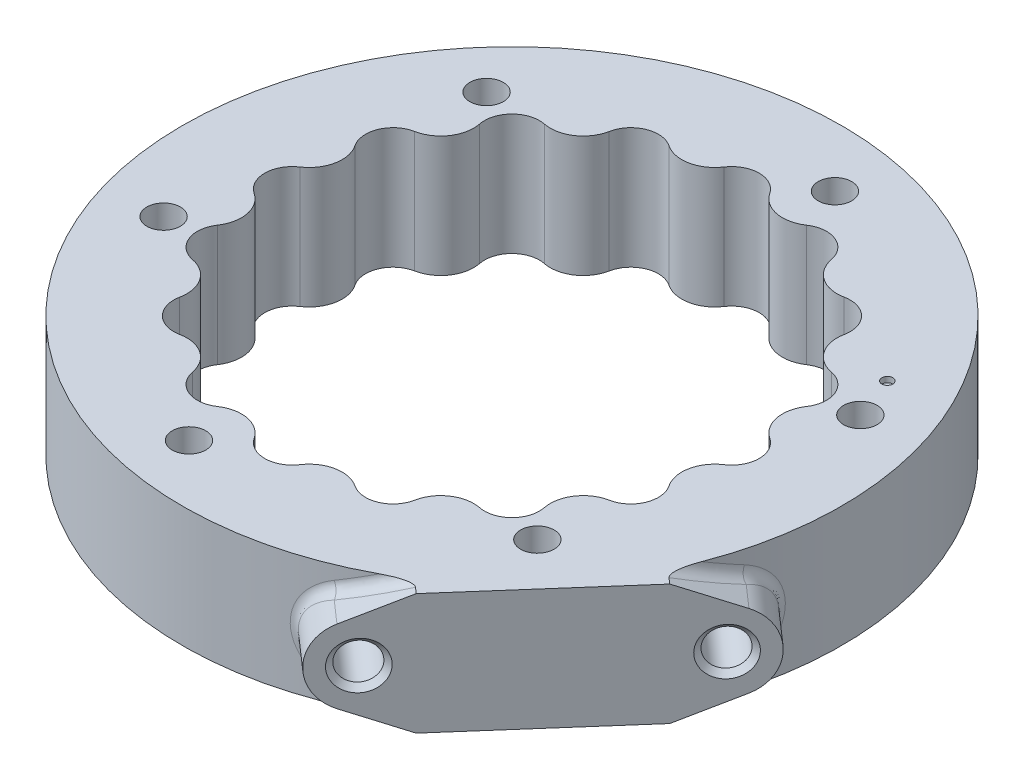
SolidWorks part; units mm, degrees
note: '?' marks a value the reader was unsure of.
ref_plane "Front Plane" through (0, 0, 0) normal (0, 0, 1) x (1, 0, 0)
ref_plane "Top Plane" through (0, 0, 0) normal (0, 1, 0) x (1, 0, 0)
ref_plane "Right Plane" through (0, 0, 0) normal (1, 0, 0) x (0, 0, -1)
sketch "Sketch1" plane through (0, 0, 0) normal (0, 1, 0) x (1, 0, 0)
  arc A0 (-31.5919, 24.5347) -> (-34.7568, 19.7981) centre (0, 0) ccw
  arc A1 (4.9902, 39.6875) -> (-4.9902, 39.6875) centre (0, 40) ccw
  arc A2 (19.7981, 34.7568) -> (10.5774, 38.5761) centre (15.3073, 36.9552) ccw
  arc A3 (-31.5919, 24.5347) -> (-34.7568, 19.7981) centre (0, 0) ccw construction
  arc A4 (31.5919, 24.5347) -> (24.5347, 31.5919) centre (28.2843, 28.2843) ccw
  arc A5 (-31.5919, 24.5347) -> (-34.7568, 19.7981) centre (0, 0) ccw construction
  arc A6 (38.5761, 10.5774) -> (34.7568, 19.7981) centre (36.9552, 15.3073) ccw
  arc A7 (-31.5919, 24.5347) -> (-34.7568, 19.7981) centre (0, 0) ccw construction
  arc A8 (39.6875, -4.9902) -> (39.6875, 4.9902) centre (40, 0) ccw
  arc A9 (-31.5919, 24.5347) -> (-34.7568, 19.7981) centre (0, 0) ccw construction
  arc A10 (34.7568, -19.7981) -> (38.5761, -10.5774) centre (36.9552, -15.3073) ccw
  arc A11 (-31.5919, 24.5347) -> (-34.7568, 19.7981) centre (0, 0) ccw construction
  arc A12 (24.5347, -31.5919) -> (31.5919, -24.5347) centre (28.2843, -28.2843) ccw
  arc A13 (-31.5919, 24.5347) -> (-34.7568, 19.7981) centre (0, 0) ccw construction
  arc A14 (10.5774, -38.5761) -> (19.7981, -34.7568) centre (15.3073, -36.9552) ccw
  arc A15 (-31.5919, 24.5347) -> (-34.7568, 19.7981) centre (0, 0) ccw construction
  arc A16 (-4.9902, -39.6875) -> (4.9902, -39.6875) centre (0, -40) ccw
  arc A17 (-31.5919, 24.5347) -> (-34.7568, 19.7981) centre (0, 0) ccw construction
  arc A18 (-19.7981, -34.7568) -> (-10.5774, -38.5761) centre (-15.3073, -36.9552) ccw
  arc A19 (-31.5919, 24.5347) -> (-34.7568, 19.7981) centre (0, 0) ccw construction
  arc A20 (-31.5919, -24.5347) -> (-24.5347, -31.5919) centre (-28.2843, -28.2843) ccw
  arc A21 (-31.5919, 24.5347) -> (-34.7568, 19.7981) centre (0, 0) ccw construction
  arc A22 (-38.5761, -10.5774) -> (-34.7568, -19.7981) centre (-36.9552, -15.3073) ccw
  arc A23 (-31.5919, 24.5347) -> (-34.7568, 19.7981) centre (0, 0) ccw construction
  arc A24 (-39.6875, 4.9902) -> (-39.6875, -4.9902) centre (-40, 0) ccw
  arc A25 (-31.5919, 24.5347) -> (-34.7568, 19.7981) centre (0, 0) ccw construction
  arc A26 (-34.7568, 19.7981) -> (-38.5761, 10.5774) centre (-36.9552, 15.3073) ccw
  arc A27 (-31.5919, 24.5347) -> (-34.7568, 19.7981) centre (0, 0) ccw construction
  arc A28 (-24.5347, 31.5919) -> (-31.5919, 24.5347) centre (-28.2843, 28.2843) ccw
  arc A29 (-31.5919, 24.5347) -> (-34.7568, 19.7981) centre (0, 0) ccw construction
  arc A30 (-10.5774, 38.5761) -> (-19.7981, 34.7568) centre (-15.3073, 36.9552) ccw
  arc A31 (-31.5919, 24.5347) -> (-34.7568, 19.7981) centre (0, 0) ccw construction
  circle A32 centre (0, 0) radius 60
  arc A33 (-19.7981, 34.7568) -> (-24.5347, 31.5919) centre (0, 0) ccw
  arc A34 (-19.7981, 34.7568) -> (-24.5347, 31.5919) centre (0, 0) ccw construction
  arc A35 (-19.7981, 34.7568) -> (-24.5347, 31.5919) centre (0, 0) ccw construction
  arc A36 (-19.7981, 34.7568) -> (-24.5347, 31.5919) centre (0, 0) ccw construction
  arc A37 (-19.7981, 34.7568) -> (-24.5347, 31.5919) centre (0, 0) ccw construction
  arc A38 (-19.7981, 34.7568) -> (-24.5347, 31.5919) centre (0, 0) ccw construction
  arc A39 (-19.7981, 34.7568) -> (-24.5347, 31.5919) centre (0, 0) ccw construction
  arc A40 (-19.7981, 34.7568) -> (-24.5347, 31.5919) centre (0, 0) ccw construction
  arc A41 (-19.7981, 34.7568) -> (-24.5347, 31.5919) centre (0, 0) ccw construction
  arc A42 (-19.7981, 34.7568) -> (-24.5347, 31.5919) centre (0, 0) ccw construction
  arc A43 (-19.7981, 34.7568) -> (-24.5347, 31.5919) centre (0, 0) ccw construction
  arc A44 (-19.7981, 34.7568) -> (-24.5347, 31.5919) centre (0, 0) ccw construction
  arc A45 (-19.7981, 34.7568) -> (-24.5347, 31.5919) centre (0, 0) ccw construction
  arc A46 (-19.7981, 34.7568) -> (-24.5347, 31.5919) centre (0, 0) ccw construction
  arc A47 (-19.7981, 34.7568) -> (-24.5347, 31.5919) centre (0, 0) ccw construction
  arc A48 (-19.7981, 34.7568) -> (-24.5347, 31.5919) centre (0, 0) ccw construction
  arc A49 (-4.9902, 39.6875) -> (-10.5774, 38.5761) centre (0, 0) ccw
  arc A50 (-4.9902, 39.6875) -> (-10.5774, 38.5761) centre (0, 0) ccw construction
  arc A51 (-4.9902, 39.6875) -> (-10.5774, 38.5761) centre (0, 0) ccw construction
  arc A52 (-4.9902, 39.6875) -> (-10.5774, 38.5761) centre (0, 0) ccw construction
  arc A53 (-4.9902, 39.6875) -> (-10.5774, 38.5761) centre (0, 0) ccw construction
  arc A54 (-4.9902, 39.6875) -> (-10.5774, 38.5761) centre (0, 0) ccw construction
  arc A55 (-4.9902, 39.6875) -> (-10.5774, 38.5761) centre (0, 0) ccw construction
  arc A56 (-4.9902, 39.6875) -> (-10.5774, 38.5761) centre (0, 0) ccw construction
  arc A57 (-4.9902, 39.6875) -> (-10.5774, 38.5761) centre (0, 0) ccw construction
  arc A58 (-4.9902, 39.6875) -> (-10.5774, 38.5761) centre (0, 0) ccw construction
  arc A59 (-4.9902, 39.6875) -> (-10.5774, 38.5761) centre (0, 0) ccw construction
  arc A60 (-4.9902, 39.6875) -> (-10.5774, 38.5761) centre (0, 0) ccw construction
  arc A61 (-4.9902, 39.6875) -> (-10.5774, 38.5761) centre (0, 0) ccw construction
  arc A62 (-4.9902, 39.6875) -> (-10.5774, 38.5761) centre (0, 0) ccw construction
  arc A63 (-4.9902, 39.6875) -> (-10.5774, 38.5761) centre (0, 0) ccw construction
  arc A64 (-4.9902, 39.6875) -> (-10.5774, 38.5761) centre (0, 0) ccw construction
  arc A65 (10.5774, 38.5761) -> (4.9902, 39.6875) centre (0, 0) ccw
  arc A66 (10.5774, 38.5761) -> (4.9902, 39.6875) centre (0, 0) ccw construction
  arc A67 (10.5774, 38.5761) -> (4.9902, 39.6875) centre (0, 0) ccw construction
  arc A68 (10.5774, 38.5761) -> (4.9902, 39.6875) centre (0, 0) ccw construction
  arc A69 (10.5774, 38.5761) -> (4.9902, 39.6875) centre (0, 0) ccw construction
  arc A70 (10.5774, 38.5761) -> (4.9902, 39.6875) centre (0, 0) ccw construction
  arc A71 (10.5774, 38.5761) -> (4.9902, 39.6875) centre (0, 0) ccw construction
  arc A72 (10.5774, 38.5761) -> (4.9902, 39.6875) centre (0, 0) ccw construction
  arc A73 (10.5774, 38.5761) -> (4.9902, 39.6875) centre (0, 0) ccw construction
  arc A74 (10.5774, 38.5761) -> (4.9902, 39.6875) centre (0, 0) ccw construction
  arc A75 (10.5774, 38.5761) -> (4.9902, 39.6875) centre (0, 0) ccw construction
  arc A76 (10.5774, 38.5761) -> (4.9902, 39.6875) centre (0, 0) ccw construction
  arc A77 (10.5774, 38.5761) -> (4.9902, 39.6875) centre (0, 0) ccw construction
  arc A78 (10.5774, 38.5761) -> (4.9902, 39.6875) centre (0, 0) ccw construction
  arc A79 (10.5774, 38.5761) -> (4.9902, 39.6875) centre (0, 0) ccw construction
  arc A80 (10.5774, 38.5761) -> (4.9902, 39.6875) centre (0, 0) ccw construction
  arc A81 (24.5347, 31.5919) -> (19.7981, 34.7568) centre (0, 0) ccw
  arc A82 (24.5347, 31.5919) -> (19.7981, 34.7568) centre (0, 0) ccw construction
  arc A83 (24.5347, 31.5919) -> (19.7981, 34.7568) centre (0, 0) ccw construction
  arc A84 (24.5347, 31.5919) -> (19.7981, 34.7568) centre (0, 0) ccw construction
  arc A85 (24.5347, 31.5919) -> (19.7981, 34.7568) centre (0, 0) ccw construction
  arc A86 (24.5347, 31.5919) -> (19.7981, 34.7568) centre (0, 0) ccw construction
  arc A87 (24.5347, 31.5919) -> (19.7981, 34.7568) centre (0, 0) ccw construction
  arc A88 (24.5347, 31.5919) -> (19.7981, 34.7568) centre (0, 0) ccw construction
  arc A89 (24.5347, 31.5919) -> (19.7981, 34.7568) centre (0, 0) ccw construction
  arc A90 (24.5347, 31.5919) -> (19.7981, 34.7568) centre (0, 0) ccw construction
  arc A91 (24.5347, 31.5919) -> (19.7981, 34.7568) centre (0, 0) ccw construction
  arc A92 (24.5347, 31.5919) -> (19.7981, 34.7568) centre (0, 0) ccw construction
  arc A93 (24.5347, 31.5919) -> (19.7981, 34.7568) centre (0, 0) ccw construction
  arc A94 (24.5347, 31.5919) -> (19.7981, 34.7568) centre (0, 0) ccw construction
  arc A95 (24.5347, 31.5919) -> (19.7981, 34.7568) centre (0, 0) ccw construction
  arc A96 (24.5347, 31.5919) -> (19.7981, 34.7568) centre (0, 0) ccw construction
  arc A97 (34.7568, 19.7981) -> (31.5919, 24.5347) centre (0, 0) ccw
  arc A98 (34.7568, 19.7981) -> (31.5919, 24.5347) centre (0, 0) ccw construction
  arc A99 (34.7568, 19.7981) -> (31.5919, 24.5347) centre (0, 0) ccw construction
  arc A100 (34.7568, 19.7981) -> (31.5919, 24.5347) centre (0, 0) ccw construction
  arc A101 (34.7568, 19.7981) -> (31.5919, 24.5347) centre (0, 0) ccw construction
  arc A102 (34.7568, 19.7981) -> (31.5919, 24.5347) centre (0, 0) ccw construction
  arc A103 (34.7568, 19.7981) -> (31.5919, 24.5347) centre (0, 0) ccw construction
  arc A104 (34.7568, 19.7981) -> (31.5919, 24.5347) centre (0, 0) ccw construction
  arc A105 (34.7568, 19.7981) -> (31.5919, 24.5347) centre (0, 0) ccw construction
  arc A106 (34.7568, 19.7981) -> (31.5919, 24.5347) centre (0, 0) ccw construction
  arc A107 (34.7568, 19.7981) -> (31.5919, 24.5347) centre (0, 0) ccw construction
  arc A108 (34.7568, 19.7981) -> (31.5919, 24.5347) centre (0, 0) ccw construction
  arc A109 (34.7568, 19.7981) -> (31.5919, 24.5347) centre (0, 0) ccw construction
  arc A110 (34.7568, 19.7981) -> (31.5919, 24.5347) centre (0, 0) ccw construction
  arc A111 (34.7568, 19.7981) -> (31.5919, 24.5347) centre (0, 0) ccw construction
  arc A112 (34.7568, 19.7981) -> (31.5919, 24.5347) centre (0, 0) ccw construction
  arc A113 (39.6875, 4.9902) -> (38.5761, 10.5774) centre (0, 0) ccw
  arc A114 (39.6875, 4.9902) -> (38.5761, 10.5774) centre (0, 0) ccw construction
  arc A115 (39.6875, 4.9902) -> (38.5761, 10.5774) centre (0, 0) ccw construction
  arc A116 (39.6875, 4.9902) -> (38.5761, 10.5774) centre (0, 0) ccw construction
  arc A117 (39.6875, 4.9902) -> (38.5761, 10.5774) centre (0, 0) ccw construction
  arc A118 (39.6875, 4.9902) -> (38.5761, 10.5774) centre (0, 0) ccw construction
  arc A119 (39.6875, 4.9902) -> (38.5761, 10.5774) centre (0, 0) ccw construction
  arc A120 (39.6875, 4.9902) -> (38.5761, 10.5774) centre (0, 0) ccw construction
  arc A121 (39.6875, 4.9902) -> (38.5761, 10.5774) centre (0, 0) ccw construction
  arc A122 (39.6875, 4.9902) -> (38.5761, 10.5774) centre (0, 0) ccw construction
  arc A123 (39.6875, 4.9902) -> (38.5761, 10.5774) centre (0, 0) ccw construction
  arc A124 (39.6875, 4.9902) -> (38.5761, 10.5774) centre (0, 0) ccw construction
  arc A125 (39.6875, 4.9902) -> (38.5761, 10.5774) centre (0, 0) ccw construction
  arc A126 (39.6875, 4.9902) -> (38.5761, 10.5774) centre (0, 0) ccw construction
  arc A127 (39.6875, 4.9902) -> (38.5761, 10.5774) centre (0, 0) ccw construction
  arc A128 (39.6875, 4.9902) -> (38.5761, 10.5774) centre (0, 0) ccw construction
  arc A129 (38.5761, -10.5774) -> (39.6875, -4.9902) centre (0, 0) ccw
  arc A130 (38.5761, -10.5774) -> (39.6875, -4.9902) centre (0, 0) ccw construction
  arc A131 (38.5761, -10.5774) -> (39.6875, -4.9902) centre (0, 0) ccw construction
  arc A132 (38.5761, -10.5774) -> (39.6875, -4.9902) centre (0, 0) ccw construction
  arc A133 (38.5761, -10.5774) -> (39.6875, -4.9902) centre (0, 0) ccw construction
  arc A134 (38.5761, -10.5774) -> (39.6875, -4.9902) centre (0, 0) ccw construction
  arc A135 (38.5761, -10.5774) -> (39.6875, -4.9902) centre (0, 0) ccw construction
  arc A136 (38.5761, -10.5774) -> (39.6875, -4.9902) centre (0, 0) ccw construction
  arc A137 (38.5761, -10.5774) -> (39.6875, -4.9902) centre (0, 0) ccw construction
  arc A138 (38.5761, -10.5774) -> (39.6875, -4.9902) centre (0, 0) ccw construction
  arc A139 (38.5761, -10.5774) -> (39.6875, -4.9902) centre (0, 0) ccw construction
  arc A140 (38.5761, -10.5774) -> (39.6875, -4.9902) centre (0, 0) ccw construction
  arc A141 (38.5761, -10.5774) -> (39.6875, -4.9902) centre (0, 0) ccw construction
  arc A142 (38.5761, -10.5774) -> (39.6875, -4.9902) centre (0, 0) ccw construction
  arc A143 (38.5761, -10.5774) -> (39.6875, -4.9902) centre (0, 0) ccw construction
  arc A144 (38.5761, -10.5774) -> (39.6875, -4.9902) centre (0, 0) ccw construction
  arc A145 (31.5919, -24.5347) -> (34.7568, -19.7981) centre (0, 0) ccw
  arc A146 (31.5919, -24.5347) -> (34.7568, -19.7981) centre (0, 0) ccw construction
  arc A147 (31.5919, -24.5347) -> (34.7568, -19.7981) centre (0, 0) ccw construction
  arc A148 (31.5919, -24.5347) -> (34.7568, -19.7981) centre (0, 0) ccw construction
  arc A149 (31.5919, -24.5347) -> (34.7568, -19.7981) centre (0, 0) ccw construction
  arc A150 (31.5919, -24.5347) -> (34.7568, -19.7981) centre (0, 0) ccw construction
  arc A151 (31.5919, -24.5347) -> (34.7568, -19.7981) centre (0, 0) ccw construction
  arc A152 (31.5919, -24.5347) -> (34.7568, -19.7981) centre (0, 0) ccw construction
  arc A153 (31.5919, -24.5347) -> (34.7568, -19.7981) centre (0, 0) ccw construction
  arc A154 (31.5919, -24.5347) -> (34.7568, -19.7981) centre (0, 0) ccw construction
  arc A155 (31.5919, -24.5347) -> (34.7568, -19.7981) centre (0, 0) ccw construction
  arc A156 (31.5919, -24.5347) -> (34.7568, -19.7981) centre (0, 0) ccw construction
  arc A157 (31.5919, -24.5347) -> (34.7568, -19.7981) centre (0, 0) ccw construction
  arc A158 (31.5919, -24.5347) -> (34.7568, -19.7981) centre (0, 0) ccw construction
  arc A159 (31.5919, -24.5347) -> (34.7568, -19.7981) centre (0, 0) ccw construction
  arc A160 (31.5919, -24.5347) -> (34.7568, -19.7981) centre (0, 0) ccw construction
  arc A161 (19.7981, -34.7568) -> (24.5347, -31.5919) centre (0, 0) ccw
  arc A162 (19.7981, -34.7568) -> (24.5347, -31.5919) centre (0, 0) ccw construction
  arc A163 (19.7981, -34.7568) -> (24.5347, -31.5919) centre (0, 0) ccw construction
  arc A164 (19.7981, -34.7568) -> (24.5347, -31.5919) centre (0, 0) ccw construction
  arc A165 (19.7981, -34.7568) -> (24.5347, -31.5919) centre (0, 0) ccw construction
  arc A166 (19.7981, -34.7568) -> (24.5347, -31.5919) centre (0, 0) ccw construction
  arc A167 (19.7981, -34.7568) -> (24.5347, -31.5919) centre (0, 0) ccw construction
  arc A168 (19.7981, -34.7568) -> (24.5347, -31.5919) centre (0, 0) ccw construction
  arc A169 (19.7981, -34.7568) -> (24.5347, -31.5919) centre (0, 0) ccw construction
  arc A170 (19.7981, -34.7568) -> (24.5347, -31.5919) centre (0, 0) ccw construction
  arc A171 (19.7981, -34.7568) -> (24.5347, -31.5919) centre (0, 0) ccw construction
  arc A172 (19.7981, -34.7568) -> (24.5347, -31.5919) centre (0, 0) ccw construction
  arc A173 (19.7981, -34.7568) -> (24.5347, -31.5919) centre (0, 0) ccw construction
  arc A174 (19.7981, -34.7568) -> (24.5347, -31.5919) centre (0, 0) ccw construction
  arc A175 (19.7981, -34.7568) -> (24.5347, -31.5919) centre (0, 0) ccw construction
  arc A176 (19.7981, -34.7568) -> (24.5347, -31.5919) centre (0, 0) ccw construction
  arc A177 (4.9902, -39.6875) -> (10.5774, -38.5761) centre (0, 0) ccw
  arc A178 (4.9902, -39.6875) -> (10.5774, -38.5761) centre (0, 0) ccw construction
  arc A179 (4.9902, -39.6875) -> (10.5774, -38.5761) centre (0, 0) ccw construction
  arc A180 (4.9902, -39.6875) -> (10.5774, -38.5761) centre (0, 0) ccw construction
  arc A181 (4.9902, -39.6875) -> (10.5774, -38.5761) centre (0, 0) ccw construction
  arc A182 (4.9902, -39.6875) -> (10.5774, -38.5761) centre (0, 0) ccw construction
  arc A183 (4.9902, -39.6875) -> (10.5774, -38.5761) centre (0, 0) ccw construction
  arc A184 (4.9902, -39.6875) -> (10.5774, -38.5761) centre (0, 0) ccw construction
  arc A185 (4.9902, -39.6875) -> (10.5774, -38.5761) centre (0, 0) ccw construction
  arc A186 (4.9902, -39.6875) -> (10.5774, -38.5761) centre (0, 0) ccw construction
  arc A187 (4.9902, -39.6875) -> (10.5774, -38.5761) centre (0, 0) ccw construction
  arc A188 (4.9902, -39.6875) -> (10.5774, -38.5761) centre (0, 0) ccw construction
  arc A189 (4.9902, -39.6875) -> (10.5774, -38.5761) centre (0, 0) ccw construction
  arc A190 (4.9902, -39.6875) -> (10.5774, -38.5761) centre (0, 0) ccw construction
  arc A191 (4.9902, -39.6875) -> (10.5774, -38.5761) centre (0, 0) ccw construction
  arc A192 (4.9902, -39.6875) -> (10.5774, -38.5761) centre (0, 0) ccw construction
  arc A193 (-10.5774, -38.5761) -> (-4.9902, -39.6875) centre (0, 0) ccw
  arc A194 (-10.5774, -38.5761) -> (-4.9902, -39.6875) centre (0, 0) ccw construction
  arc A195 (-10.5774, -38.5761) -> (-4.9902, -39.6875) centre (0, 0) ccw construction
  arc A196 (-10.5774, -38.5761) -> (-4.9902, -39.6875) centre (0, 0) ccw construction
  arc A197 (-10.5774, -38.5761) -> (-4.9902, -39.6875) centre (0, 0) ccw construction
  arc A198 (-10.5774, -38.5761) -> (-4.9902, -39.6875) centre (0, 0) ccw construction
  arc A199 (-10.5774, -38.5761) -> (-4.9902, -39.6875) centre (0, 0) ccw construction
  arc A200 (-10.5774, -38.5761) -> (-4.9902, -39.6875) centre (0, 0) ccw construction
  arc A201 (-10.5774, -38.5761) -> (-4.9902, -39.6875) centre (0, 0) ccw construction
  arc A202 (-10.5774, -38.5761) -> (-4.9902, -39.6875) centre (0, 0) ccw construction
  arc A203 (-10.5774, -38.5761) -> (-4.9902, -39.6875) centre (0, 0) ccw construction
  arc A204 (-10.5774, -38.5761) -> (-4.9902, -39.6875) centre (0, 0) ccw construction
  arc A205 (-10.5774, -38.5761) -> (-4.9902, -39.6875) centre (0, 0) ccw construction
  arc A206 (-10.5774, -38.5761) -> (-4.9902, -39.6875) centre (0, 0) ccw construction
  arc A207 (-10.5774, -38.5761) -> (-4.9902, -39.6875) centre (0, 0) ccw construction
  arc A208 (-10.5774, -38.5761) -> (-4.9902, -39.6875) centre (0, 0) ccw construction
  arc A209 (-24.5347, -31.5919) -> (-19.7981, -34.7568) centre (0, 0) ccw
  arc A210 (-24.5347, -31.5919) -> (-19.7981, -34.7568) centre (0, 0) ccw construction
  arc A211 (-24.5347, -31.5919) -> (-19.7981, -34.7568) centre (0, 0) ccw construction
  arc A212 (-24.5347, -31.5919) -> (-19.7981, -34.7568) centre (0, 0) ccw construction
  arc A213 (-24.5347, -31.5919) -> (-19.7981, -34.7568) centre (0, 0) ccw construction
  arc A214 (-24.5347, -31.5919) -> (-19.7981, -34.7568) centre (0, 0) ccw construction
  arc A215 (-24.5347, -31.5919) -> (-19.7981, -34.7568) centre (0, 0) ccw construction
  arc A216 (-24.5347, -31.5919) -> (-19.7981, -34.7568) centre (0, 0) ccw construction
  arc A217 (-24.5347, -31.5919) -> (-19.7981, -34.7568) centre (0, 0) ccw construction
  arc A218 (-24.5347, -31.5919) -> (-19.7981, -34.7568) centre (0, 0) ccw construction
  arc A219 (-24.5347, -31.5919) -> (-19.7981, -34.7568) centre (0, 0) ccw construction
  arc A220 (-24.5347, -31.5919) -> (-19.7981, -34.7568) centre (0, 0) ccw construction
  arc A221 (-24.5347, -31.5919) -> (-19.7981, -34.7568) centre (0, 0) ccw construction
  arc A222 (-24.5347, -31.5919) -> (-19.7981, -34.7568) centre (0, 0) ccw construction
  arc A223 (-24.5347, -31.5919) -> (-19.7981, -34.7568) centre (0, 0) ccw construction
  arc A224 (-24.5347, -31.5919) -> (-19.7981, -34.7568) centre (0, 0) ccw construction
  arc A225 (-34.7568, -19.7981) -> (-31.5919, -24.5347) centre (0, 0) ccw
  arc A226 (-34.7568, -19.7981) -> (-31.5919, -24.5347) centre (0, 0) ccw construction
  arc A227 (-34.7568, -19.7981) -> (-31.5919, -24.5347) centre (0, 0) ccw construction
  arc A228 (-34.7568, -19.7981) -> (-31.5919, -24.5347) centre (0, 0) ccw construction
  arc A229 (-34.7568, -19.7981) -> (-31.5919, -24.5347) centre (0, 0) ccw construction
  arc A230 (-34.7568, -19.7981) -> (-31.5919, -24.5347) centre (0, 0) ccw construction
  arc A231 (-34.7568, -19.7981) -> (-31.5919, -24.5347) centre (0, 0) ccw construction
  arc A232 (-34.7568, -19.7981) -> (-31.5919, -24.5347) centre (0, 0) ccw construction
  arc A233 (-34.7568, -19.7981) -> (-31.5919, -24.5347) centre (0, 0) ccw construction
  arc A234 (-34.7568, -19.7981) -> (-31.5919, -24.5347) centre (0, 0) ccw construction
  arc A235 (-34.7568, -19.7981) -> (-31.5919, -24.5347) centre (0, 0) ccw construction
  arc A236 (-34.7568, -19.7981) -> (-31.5919, -24.5347) centre (0, 0) ccw construction
  arc A237 (-34.7568, -19.7981) -> (-31.5919, -24.5347) centre (0, 0) ccw construction
  arc A238 (-34.7568, -19.7981) -> (-31.5919, -24.5347) centre (0, 0) ccw construction
  arc A239 (-34.7568, -19.7981) -> (-31.5919, -24.5347) centre (0, 0) ccw construction
  arc A240 (-34.7568, -19.7981) -> (-31.5919, -24.5347) centre (0, 0) ccw construction
  arc A241 (-39.6875, -4.9902) -> (-38.5761, -10.5774) centre (0, 0) ccw
  arc A242 (-39.6875, -4.9902) -> (-38.5761, -10.5774) centre (0, 0) ccw construction
  arc A243 (-39.6875, -4.9902) -> (-38.5761, -10.5774) centre (0, 0) ccw construction
  arc A244 (-39.6875, -4.9902) -> (-38.5761, -10.5774) centre (0, 0) ccw construction
  arc A245 (-39.6875, -4.9902) -> (-38.5761, -10.5774) centre (0, 0) ccw construction
  arc A246 (-39.6875, -4.9902) -> (-38.5761, -10.5774) centre (0, 0) ccw construction
  arc A247 (-39.6875, -4.9902) -> (-38.5761, -10.5774) centre (0, 0) ccw construction
  arc A248 (-39.6875, -4.9902) -> (-38.5761, -10.5774) centre (0, 0) ccw construction
  arc A249 (-39.6875, -4.9902) -> (-38.5761, -10.5774) centre (0, 0) ccw construction
  arc A250 (-39.6875, -4.9902) -> (-38.5761, -10.5774) centre (0, 0) ccw construction
  arc A251 (-39.6875, -4.9902) -> (-38.5761, -10.5774) centre (0, 0) ccw construction
  arc A252 (-39.6875, -4.9902) -> (-38.5761, -10.5774) centre (0, 0) ccw construction
  arc A253 (-39.6875, -4.9902) -> (-38.5761, -10.5774) centre (0, 0) ccw construction
  arc A254 (-39.6875, -4.9902) -> (-38.5761, -10.5774) centre (0, 0) ccw construction
  arc A255 (-39.6875, -4.9902) -> (-38.5761, -10.5774) centre (0, 0) ccw construction
  arc A256 (-39.6875, -4.9902) -> (-38.5761, -10.5774) centre (0, 0) ccw construction
  arc A257 (-38.5761, 10.5774) -> (-39.6875, 4.9902) centre (0, 0) ccw
  arc A258 (-38.5761, 10.5774) -> (-39.6875, 4.9902) centre (0, 0) ccw construction
  arc A259 (-38.5761, 10.5774) -> (-39.6875, 4.9902) centre (0, 0) ccw construction
  arc A260 (-38.5761, 10.5774) -> (-39.6875, 4.9902) centre (0, 0) ccw construction
  arc A261 (-38.5761, 10.5774) -> (-39.6875, 4.9902) centre (0, 0) ccw construction
  arc A262 (-38.5761, 10.5774) -> (-39.6875, 4.9902) centre (0, 0) ccw construction
  arc A263 (-38.5761, 10.5774) -> (-39.6875, 4.9902) centre (0, 0) ccw construction
  arc A264 (-38.5761, 10.5774) -> (-39.6875, 4.9902) centre (0, 0) ccw construction
  arc A265 (-38.5761, 10.5774) -> (-39.6875, 4.9902) centre (0, 0) ccw construction
  arc A266 (-38.5761, 10.5774) -> (-39.6875, 4.9902) centre (0, 0) ccw construction
  arc A267 (-38.5761, 10.5774) -> (-39.6875, 4.9902) centre (0, 0) ccw construction
  arc A268 (-38.5761, 10.5774) -> (-39.6875, 4.9902) centre (0, 0) ccw construction
  arc A269 (-38.5761, 10.5774) -> (-39.6875, 4.9902) centre (0, 0) ccw construction
  arc A270 (-38.5761, 10.5774) -> (-39.6875, 4.9902) centre (0, 0) ccw construction
  arc A271 (-38.5761, 10.5774) -> (-39.6875, 4.9902) centre (0, 0) ccw construction
  arc A272 (-38.5761, 10.5774) -> (-39.6875, 4.9902) centre (0, 0) ccw construction
  point P52 (0, 0)
  dimension "D1" = 80
  dimension "D2" = 10
  dimension "D4" = 120
  dimension "D3" = 16
extrude "Boss-Extrude1" add sketch "Sketch1" along normal blind 22
fillet "Fillet1" radius 5 32 edges at (-31.5919, 11, -24.5347) (-34.7568, 11, -19.7981) (10.5774, 11, 38.5761) (4.9902, 11, 39.6875) (-4.9902, 11, 39.6875) (-10.5774, 11, 38.5761) (-19.7981, 11, 34.7568) (-24.5347, 11, 31.5919) (-31.5919, 11, 24.5347) (-34.7568, 11, 19.7981) (-38.5761, 11, 10.5774) (-39.6875, 11, 4.9902) (-39.6875, 11, -4.9902) (-38.5761, 11, -10.5774) (19.7981, 11, 34.7568) (24.5347, 11, 31.5919) (31.5919, 11, 24.5347) (34.7568, 11, 19.7981) (38.5761, 11, 10.5774) (39.6875, 11, 4.9902) (39.6875, 11, -4.9902) (38.5761, 11, -10.5774) (34.7568, 11, -19.7981) (31.5919, 11, -24.5347) (24.5347, 11, -31.5919) (19.7981, 11, -34.7568) (10.5774, 11, -38.5761) (4.9902, 11, -39.6875) (-4.9902, 11, -39.6875) (-10.5774, 11, -38.5761) (-19.7981, 11, -34.7568) (-24.5347, 11, -31.5919)
fillet "Fillet2" radius 6 16 edges at (-7.8059, 11, 39.2431) (7.8059, 11, 39.2431) (22.2294, 11, 33.2687) (33.2687, 11, 22.2294) (-22.2294, 11, 33.2687) (-33.2687, 11, 22.2294) (-39.2431, 11, 7.8059) (-39.2431, 11, -7.8059) (39.2431, 11, 7.8059) (39.2431, 11, -7.8059) (33.2687, 11, -22.2294) (22.2294, 11, -33.2687) (7.8059, 11, -39.2431) (-7.8059, 11, -39.2431) (-22.2294, 11, -33.2687) (-33.2687, 11, -22.2294)
sketch "Sketch3" plane through (0, 22, 0) normal (0, 1, 0) x (1, 0, 0)
  line L0 (7.9956, 40.1966) -> (11.7054, 58.8471) construction
  circle A0 centre (0, 0) radius 50 construction
  circle A4 centre (9.7545, 49.0393) radius 3.05
  arc A5 (4.1664, 42.7642) -> (12.5159, 41.1034) centre (9.1661, 46.0813) ccw construction
  circle A6 centre (0, 0) radius 60 construction
  circle A7 centre (47.3465, 16.072) radius 3.05
  circle A8 centre (37.592, -32.9673) radius 3.05
  circle A9 centre (-9.7545, -49.0393) radius 3.05
  circle A10 centre (-47.3465, -16.072) radius 3.05
  circle A11 centre (-37.592, 32.9673) radius 3.05
  point P13 (9.1661, 46.0813)
  point P31 (0, 0)
  dimension "D1" = 100
  dimension "D2" = 6.1
  dimension "D3" = 6
extrude "Cut-Extrude1" cut sketch "Sketch3" against normal through all
ref_axis "Axis1" through (37.592, 0, 32.9673) along (0, 1, 0)?
ref_axis "Axis2" through (-9.7545, 0, 49.0393) along (0, 1, 0)?
ref_plane "Plane1" through (13.9187, 0, 41.0033) normal (-0.3214, 0, -0.9469) x (-0.9469, 0, 0.3214)
ref_plane "Plane2" through (19.2864, 0, 56.8158) normal (0.3214, 0, 0.9469) x (0.9469, 0, -0.3214)
ref_plane "Plane3" through (19.6078, 0, 57.7627) normal (0.3214, 0, 0.9469) x (0.9469, 0, -0.3214)
ref_plane "Plane4" through (45.1104, 0, 39.5607) normal (0.7518, 0, 0.6593) x (0, -1, 0)
ref_plane "Plane5" through (45.8622, 0, 40.2201) normal (0.7518, 0, 0.6593) x (0, -1, 0)
sketch "Sketch6" plane through (48.3229, 0, 37.4142) normal (-0.7518, 0, -0.6593) x (-0.6593, 0, 0.7518)
  line L0 (-56.2679, 0) -> (63.7321, 0) construction
  line L1 (-22.8416, 17.6775) -> (-2.6943, 26.1971)
  line L2 (10.1584, 26.1971) -> (30.3057, 17.6775)
  line L3 (-22.8416, 4.3225) -> (-2.6943, -4.1971)
  line L4 (10.1584, -4.1971) -> (30.3057, 4.3225)
  arc A0 (-2.6943, -4.1971) -> (10.1584, -4.1971) centre (3.7321, 11) ccw
  arc A1 (30.3057, 4.3225) -> (30.3057, 17.6775) centre (27.4821, 11) ccw
  arc A2 (-22.8416, 17.6775) -> (-22.8416, 4.3225) centre (-20.0179, 11) ccw
  arc A3 (10.1584, 26.1971) -> (-2.6943, 26.1971) centre (3.7321, 11) ccw
  dimension "D1" = 33
  dimension "D2" = 23.75
  dimension "D3" = 23.75
  dimension "D4" = 11
extrude "Boss-Extrude3" add sketch "Sketch6" against normal up to surface (1.3451 mm away)
sketch "Sketch7" plane through (45.8622, 0, 40.2201) normal (0.7518, 0, 0.6593) x (0.6593, 0, -0.7518)
  circle A0 centre (23.75, 11) radius 3.3
  circle A1 centre (-23.75, 11) radius 3.3
  dimension "D1" = 6.6
extrude "Cut-Extrude3" cut sketch "Sketch7" against normal blind 10.5
chamfer "Chamfer2" distance 1 angle 45 2 edges at (63.6975, 11, 19.8828) (32.3786, 11, 55.5952)
fillet "Fillet3" radius 2 6 edges at (56.3102, 19.8007, 20.7161) (56.3102, 2.1993, 20.7161) (27.8889, 2.1993, 53.1245) (27.8889, 19.8007, 53.1245) (59.03, 9.4978, 10.745) (18.3581, 12.5022, 57.1225)
sketch "Sketch8" plane through (45.8622, 0, 40.2201) normal (0.7518, 0, 0.6593) x (0.6593, 0, -0.7518)
  line L1 (-16.3518, 22) -> (16.3518, 22)
  line L2 (-16.3518, 22) -> (-16.3518, 27.5)
  line L3 (-16.3518, 27.5) -> (16.3518, 27.5)
  line L4 (16.3518, 22) -> (16.3518, 27.5)
  line L6 (-16.3518, -5.5) -> (16.3518, -5.5)
  line L7 (-16.3518, -5.5) -> (-16.3518, 0)
  line L8 (-16.3518, 0) -> (16.3518, 0)
  line L9 (16.3518, -5.5) -> (16.3518, 0)
  line L10 (26.5737, 4.3225) -> (6.4263, -4.1971) construction
  line L11 (60, 22) -> (-60, 22) construction
  arc A0 (6.4263, 26.1971) -> (-6.4263, 26.1971) centre (0, 11) ccw construction
  arc A1 (-6.4263, -4.1971) -> (6.4263, -4.1971) centre (0, 11) ccw construction
extrude "Cut-Extrude4" cut sketch "Sketch8" against normal through all
sketch "Sketch9" [suppressed] plane through (0, 22, 0) normal (0, 1, 0) x (1, 0, 0)
  circle A0 centre (44.4252, 23.9053) radius 1
  dimension "D1" = 2
extrude "Cut-Extrude5" [suppressed] cut sketch "Sketch9" against normal blind 1
sketch "Sketch10" plane through (0, 22, 0) normal (0, 1, 0) x (1, 0, 0)
  circle A0 centre (44.4252, 23.9053) radius 1
  dimension "D1" = 2
extrude "Cut-Extrude6" cut sketch "Sketch10" against normal blind 1
equation "\"R_ROLL\"= 5mm"
equation "\"D_SUN\"= 80mm"
equation "\"NUM_ROLL\"= 16"
equation "\"RHO\"= 1mm"
equation "\"D_SHAFT\"= 15mm"
equation "\"D_OUTPUT\"= 40mm"
equation "\"NUM_OUT\"= 6"
equation "\"R_OUT_ROLL\"= 5mm"
equation "\"D1@Sketch1\"=\"D_SUN\""
equation "\"D2@Sketch1\"=\"R_ROLL\"*2"
equation "\"D3@Sketch1\"=\"NUM_ROLL\""
equation "\"D4@Sketch1\"=\"D_SUN\"+40"
